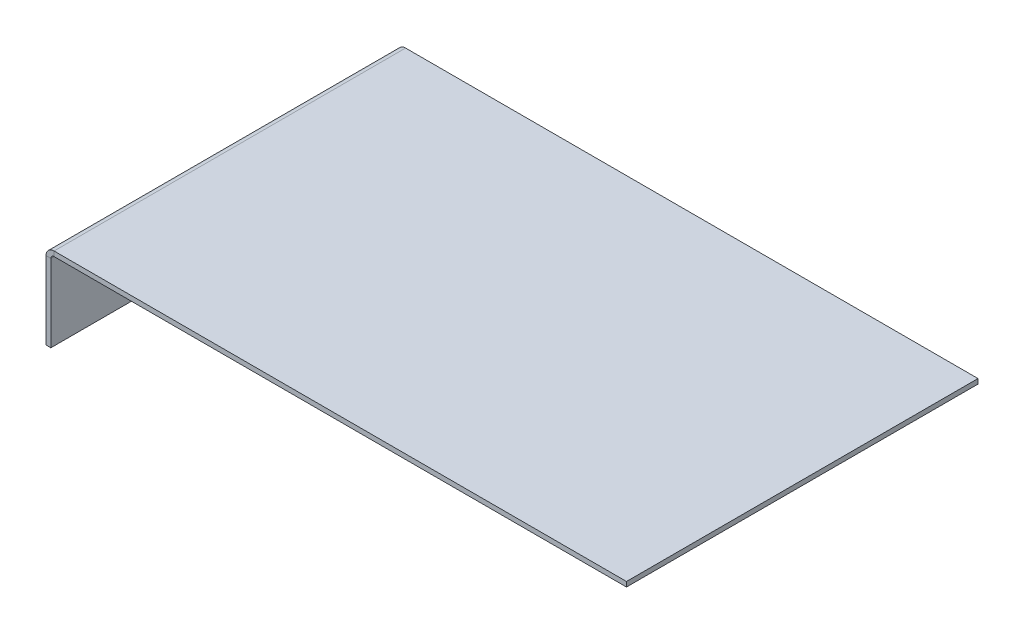
SolidWorks part; units mm, degrees
note: The reader was unsure of these and kept them because the rebuilt part matched: thickness of "基体-法兰1", "边线-法兰1", "钣金6", "钣金7"; flange length of "边线-法兰1".
ref_plane "前视基准面" through (0, 0, 0) normal (0, 0, 1) x (1, 0, 0)
ref_plane "上视基准面" through (0, 0, 0) normal (0, 1, 0) x (1, 0, 0)
ref_plane "右视基准面" through (0, 0, 0) normal (1, 0, 0) x (0, 0, -1)
other "Configuration Table"
sketch "草图1" plane through (0, 0, 0) normal (0, 1, 0) x (1, 0, 0)
  line L1 (-90, -54.5) -> (90, -54.5)
  line L2 (-90, -54.5) -> (-90, 54.5)
  line L3 (-90, 54.5) -> (90, 54.5)
  line L4 (90, -54.5) -> (90, 54.5)
  line L5 (-90, -54.5) -> (90, 54.5) construction
  line L6 (-90, 54.5) -> (90, -54.5) construction
  point P0 (0, 0)
  dimension "D1" = 109
  dimension "D2" = 180
base flange "基体-法兰1" sketch "草图1" thickness 1.5 reverse thickness direction no parameters "D1"=0.7366
edge flange "边线-法兰1" sketch "草图8" flange angle 90 flange length 26.5 bend radius 1 thickness 1.5 relief rectangular parameters "D6"=10
sketch "草图8" plane through (-90, -1.5, 0) normal (1, 0, 0) x (0, 0, 1)
  line L2 (-54.5, 0) -> (-54.5, 25)
  line L3 (-54.5, 25) -> (54.5, 25)
  line L4 (54.5, 25) -> (54.5, 0)
  line L5 (54.5, 0) -> (-54.5, 0) construction
  line L6 (54.5, 0) -> (-54.5, 0)
  dimension "D1" = 25
bend "边线折弯1" bend radius 1 bend angle 90 parameters "D5"=1
sketch "折弯-线1" plane through (0, 0, 0) normal (0, 1, 0) x (1, 0, 0)
sketch "边界框1" plane through (0, 0, 0) normal (0, 1, 0) x (1, 0, 0)
sheet metal parameters "钣金6" thickness 1.5 parameters "D1"=0.7366
flat pattern "平板型式6" [suppressed]
sketch "折弯-线2" plane through (0, 0, 0) normal (0, 1, 0) x (1, 0, 0)
sketch "边界框2" [suppressed] plane through (0, 0, 0) normal (0, 1, 0) x (1, 0, 0)
sheet metal parameters "钣金7" thickness 1.5 parameters "D1"=0.7366, "D7"=3
flat pattern "平板型式6" [suppressed]
sketch "折弯-线2" plane through (0, 0, 0) normal (0, 1, 0) x (1, 0, 0)
sketch "边界框2" [suppressed] plane through (0, 0, 0) normal (0, 1, 0) x (1, 0, 0)
bend of the flat pattern "展平-<边线折弯1>1"
